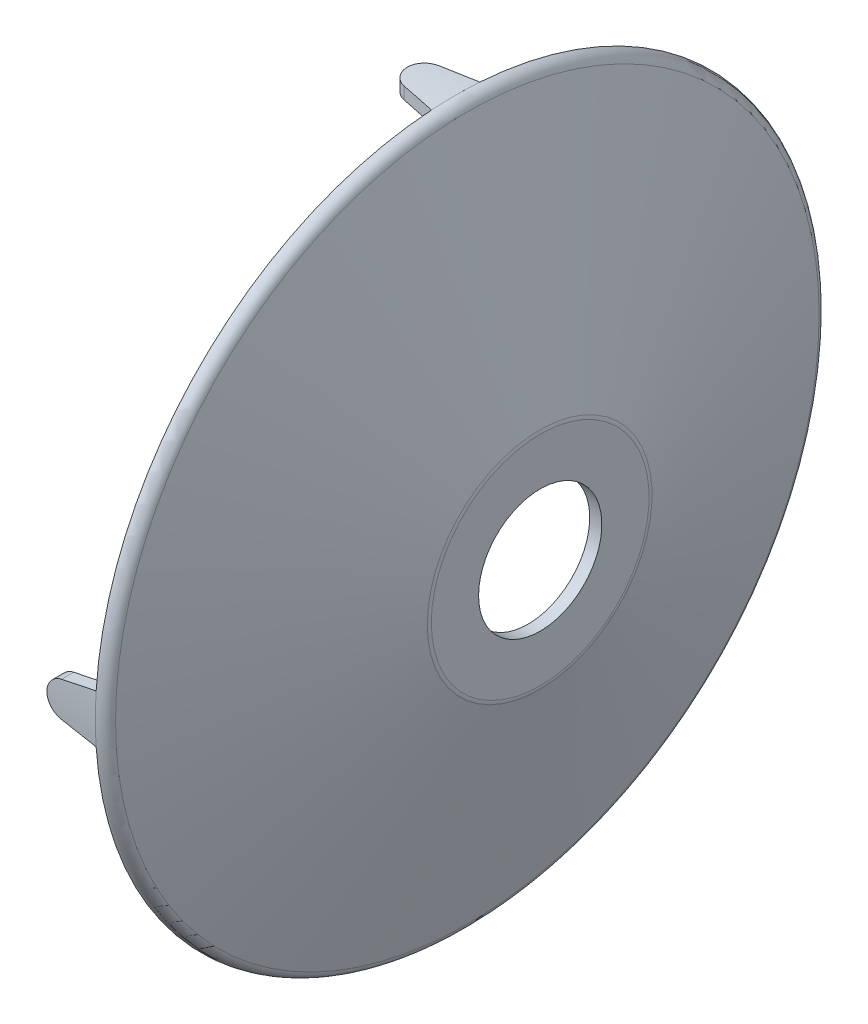
SolidWorks part; units mm, degrees
ref_plane "Front Plane" through (0, 0, 0) normal (0, 0, 1) x (1, 0, 0)
ref_plane "Top Plane" through (0, 0, 0) normal (0, 1, 0) x (1, 0, 0)
ref_plane "Right Plane" through (0, 0, 0) normal (1, 0, 0) x (0, 0, -1)
sketch "Sketch1" plane through (0, 0, 0) normal (0, 0, 1) x (1, 0, 0)
  line L0 (0, 0) -> (50000, 0) construction
  line L1 (0, 4.0386) -> (0, 7.1374)
  line L2 (-0.034, 7.3671) -> (-4.9479, 23.622)
  line L3 (-4.9479, 23.622) -> (-5.5372, 23.622)
  line L4 (-0.7937, 4.0386) -> (-0.7937, 7.02)
  line L5 (-0.8277, 7.2497) -> (-5.5372, 22.8283)
  line L7 (-0.7937, 4.0386) -> (0, 4.0386)
  line L8 (-5.5372, 23.622) -> (-5.5372, 22.8283)
  line L9 (-5.5372, 22.8283) -> (-5.5372, 22.8283) construction
  line L10 (0, 4.0386) -> (0, 7.2548) construction
  line L11 (0, 7.2548) -> (-4.9479, 23.622) construction
  line L12 (-0.7937, 7.1374) -> (-5.5372, 22.8283) construction
  line L13 (-0.7937, 4.0386) -> (-0.7937, 7.1374) construction
  arc A0 (0, 7.1374) -> (-0.034, 7.3671) centre (-0.7937, 7.1374) ccw
  arc A1 (-0.8277, 7.2497) -> (-0.7937, 7.02) centre (-1.5875, 7.02) cw
  point P11 (-0.7938, 15.5343)
  point P12 (0, 12.1281)
  point P13 (0, 0)
  point P14 (0, 0)
  point P15 (-4.9479, 23.622)
  point P19 (0, 7.2548)
  point P23 (-0.7937, 7.1374)
  point P24 (0, 4.0386)
  dimension "D6" = 0.7937
  dimension "D2" = 8.0772
  dimension "D3" = 5.5372
  dimension "D4" = 47.244
  dimension "D5" = 14.2748
  dimension "D1" = 0.7937
revolve "Revolve1" add sketch "Sketch1" angle 360 about L0 region at (-2.4754, 13.8311, 0)
sketch "Sketch2" plane through (0, 0, 0) normal (0, 0, 1) x (1, 0, 0)
  line L0 (-5.5372, 23.622) -> (-5.5372, -23.622) construction
  line L1 (-5.5372, 23.622) -> (-5.5372, 22.8283)
  line L2 (-5.5372, 23.622) -> (-8.7122, 23.622)
  line L3 (-8.7122, 23.622) -> (-8.7122, 22.8283)
  line L4 (-8.7122, 22.8283) -> (-5.5372, 22.8283)
  line L5 (0, 0) -> (-50000, 0) construction
  dimension "D1" = 0.7937
  dimension "D2" = 3.175
revolve "Revolve2" add sketch "Sketch2" angle 15 mid plane about L5
sketch "Sketch3" plane through (0, 0, 0) normal (0, 1, 0) x (1, 0, 0)
  line L0 (0, 0) -> (-50000, 0) construction
  line L1 (-5.5372, -1.5875) -> (-7.7703, -1.1462)
  line L2 (-5.5372, 23.622) -> (-5.5372, -23.622) construction
  line L3 (-7.7703, 1.1462) -> (-5.5372, 1.5875)
  line L5 (-5.5372, 1.5875) -> (-5.5372, 3.0833)
  line L6 (-5.5372, 3.0833) -> (-8.7122, 3.0833)
  line L7 (-8.7122, 3.0833) -> (-8.7122, -3.0833)
  line L8 (-8.7122, -3.0833) -> (-5.5372, -3.0833)
  line L9 (-5.5372, -3.0833) -> (-5.5372, -1.5875)
  arc A1 (-7.7703, -1.1462) -> (-8.7122, 0) centre (-7.5438, 0) cw
  arc A2 (-7.7703, 1.1462) -> (-8.7122, 0) centre (-7.5438, 0) ccw
  point P11 (-8.186, 0.7248)
  dimension "D2" = 1.1684
  dimension "D1" = 3.175
extrude "Cut-Extrude1" cut sketch "Sketch3" against normal through all both and the other way through all contours L1 A1 L7 L8 L9 | A2 L3 L5 L6 L7 region at (-7.2562, 0, 2.127) region at (-7.2562, 0, -2.127)
pattern_circular "CirPattern1" count 4 over 360 about axis through (0, 0, 0) along (-1, 0, 0) of "Revolve2", "Cut-Extrude1"
fillet "Fillet1" radius 0.7937 1 edges at (-4.9479, 0, 23.622)
